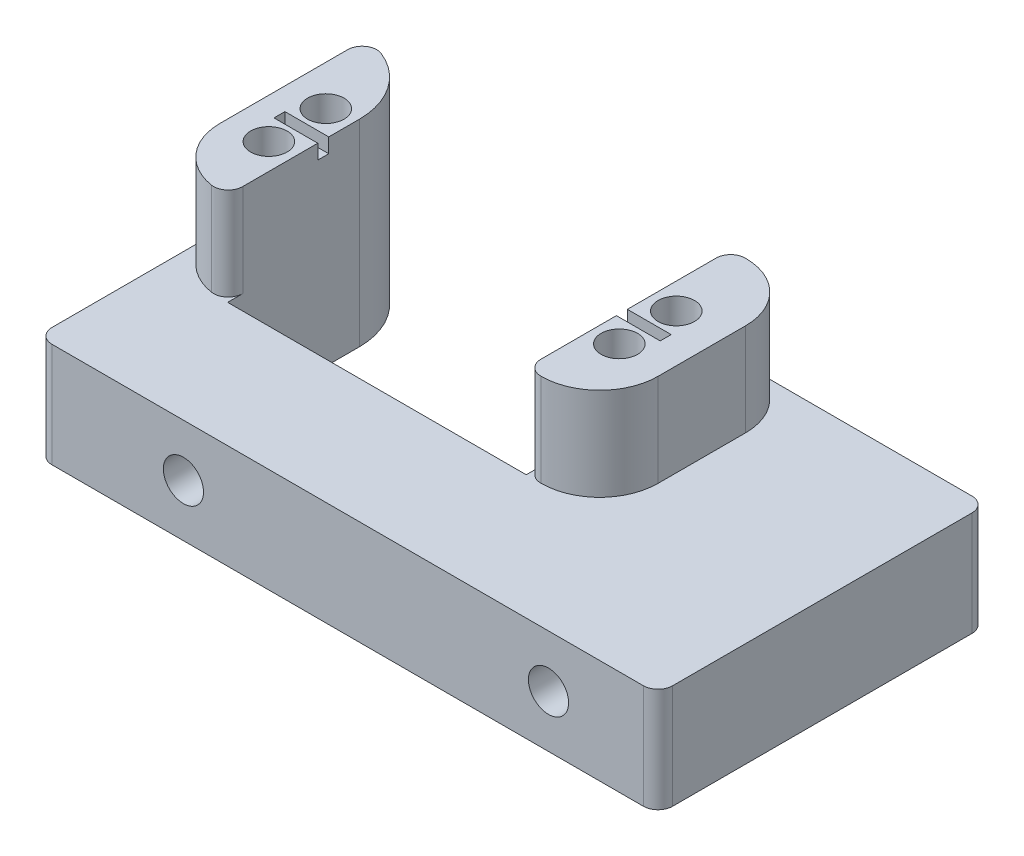
SolidWorks part; units mm, degrees
ref_plane "Front" through (0, 0, 0) normal (0, 0, 1) x (1, 0, 0)
ref_plane "Top" through (0, 0, 0) normal (0, 1, 0) x (1, 0, 0)
ref_plane "Right" through (0, 0, 0) normal (1, 0, 0) x (0, 0, -1)
sketch "Sketch1" plane through (0, 0, 0) normal (0, 1, 0) x (1, 0, 0)
  line L1 (0, 0) -> (85, 0)
  line L2 (0, 0) -> (0, 45)
  line L3 (0, 45) -> (85, 45)
  line L4 (85, 0) -> (85, 45)
  dimension "D1" = 85
  dimension "D2" = 45
extrude "Boss-Extrude1" add sketch "Sketch1" along normal blind 27
sketch "Sketch2" plane through (0, 27, 0) normal (0, 1, 0) x (1, 0, 0)
  line L0 (0, 45) -> (0, 0) construction
  line L1 (85, 45) -> (0, 45) construction
  circle A0 centre (5.5, 34) radius 2.5
  circle A1 centre (53.5, 34) radius 2.5
  circle A2 centre (53.5, 26.2) radius 2.5
  circle A3 centre (5.5, 26.2) radius 2.5
  dimension "D3" = 5
  dimension "D6" = 48
  dimension "D1" = 5.5
  dimension "D2" = 11
  dimension "D7" = 7.8
  dimension "D4" = 2
  dimension "D5" = 2
extrude "Cut-Extrude1" cut sketch "Sketch2" against normal through all
sketch "Sketch4" plane through (0, 0, 0) normal (-1, 0, 0) x (0, 0, 1)
  line L0 (-45, 27) -> (0, 27) construction
  line L1 (0, 27) -> (-17, 27)
  line L2 (0, 27) -> (0, 14.3)
  line L3 (0, 14.3) -> (-17, 14.3)
  line L4 (-17, 27) -> (-17, 14.3)
  line L5 (0, 27) -> (0, 0) construction
  dimension "D1" = 12.7
  dimension "D2" = 17
extrude "Cut-Extrude2" cut sketch "Sketch4" against normal through all
sketch "Sketch5" plane through (0, 0, -17) normal (0, 0, 1) x (1, 0, 0)
  line L0 (85, 14.3) -> (0, 14.3) construction
  line L1 (85, 27) -> (60, 27)
  line L2 (85, 27) -> (85, 14.3)
  line L3 (85, 14.3) -> (60, 14.3)
  line L4 (60, 27) -> (60, 14.3)
  dimension "D1" = 25
extrude "Cut-Extrude3" cut sketch "Sketch5" against normal through all
sketch "Sketch6" plane through (0, 27, 0) normal (0, 1, 0) x (1, 0, 0)
  line L0 (60, 17) -> (0, 17) construction
  line L1 (9.05, 17) -> (49.95, 17)
  line L2 (9.05, 17) -> (9.05, 45)
  line L3 (9.05, 45) -> (49.95, 45)
  line L4 (49.95, 17) -> (49.95, 45)
  line L5 (60, 45) -> (0, 45) construction
  line L6 (29.5, 34) -> (29.5, 45) construction
  line L7 (5.5, 34) -> (53.5, 34) construction
  circle A0 centre (5.5, 34) radius 2.5 construction
  dimension "D1" = 3.55
extrude "Cut-Extrude4" cut sketch "Sketch6" against normal through all
fillet "Fillet1" radius 10 1 edges at (9.05, 13.5, -45)
fillet "Fillet2" radius 8 3 edges at (60, 20.65, -45) (0, 20.65, -17) (60, 20.65, -17)
fillet "Fillet4" radius 2 7 edges at (9.05, 20.65, -17) (49.95, 20.65, -17) (49.95, 13.5, -45) (85, 7.15, -45) (85, 7.15, 0) (0, 7.15, 0) (0, 13.5, -45)
sketch "Sketch7" plane through (0, 0, 0) normal (0, 0, 1) x (1, 0, 0)
  line L0 (20, 0) -> (20, 14.3) construction
  line L1 (2, 0) -> (83, 0) construction
  line L2 (83, 14.3) -> (2, 14.3) construction
  line L3 (85, 14.3) -> (85, 0) construction
  circle A0 centre (70, 7.15) radius 2.75
  circle A1 centre (20, 7.15) radius 2.75
  point P4 (15.8808, 4.8102)
  point P11 (22.1942, 0)
  dimension "D3" = 5.5
  dimension "D1" = 50
  dimension "D2" = 15
extrude "Cut-Extrude5" cut sketch "Sketch7" against normal through all
sketch "Sketch8" plane through (0, 27, 0) normal (0, 1, 0) x (1, 0, 0)
  line L0 (9.05, 35.0452) -> (9.05, 19.0757) construction
  line L1 (3.05, 30.85) -> (9.05, 30.85)
  line L2 (3.05, 30.85) -> (3.05, 29.35)
  line L3 (3.05, 29.35) -> (9.05, 29.35)
  line L4 (9.05, 30.85) -> (9.05, 29.35)
  line L5 (5.5, 31.5) -> (5.5, 28.7) construction
  line L6 (5.5, 30.1) -> (9.05, 30.1) construction
  line L7 (49.95, 19) -> (49.95, 43) construction
  line L8 (49.95, 29.35) -> (55.95, 29.35)
  line L9 (49.95, 29.35) -> (49.95, 30.85)
  line L10 (49.95, 30.85) -> (55.95, 30.85)
  line L11 (55.95, 29.35) -> (55.95, 30.85)
  circle A0 centre (5.5, 34) radius 2.5 construction
  circle A1 centre (5.5, 26.2) radius 2.5 construction
  dimension "D1" = 1.5
  dimension "D2" = 6
extrude "Cut-Extrude6" cut sketch "Sketch8" against normal blind 2
